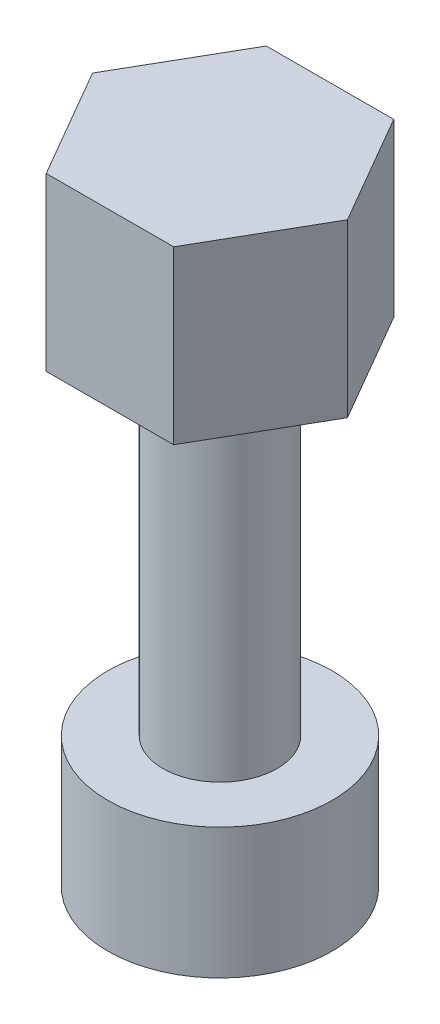
SolidWorks part; units mm, degrees
ref_plane "Front Plane" through (0, 0, 0) normal (0, 0, 1) x (1, 0, 0)
ref_plane "Top Plane" through (0, 0, 0) normal (0, 1, 0) x (1, 0, 0)
ref_plane "Right Plane" through (0, 0, 0) normal (1, 0, 0) x (0, 0, -1)
sketch "Sketch1" plane through (0, 0, 0) normal (0, 1, 0) x (1, 0, 0)
  circle A0 centre (0, 0) radius 2.75
  dimension "D1" = 5.5
extrude "Boss-Extrude1" add sketch "Sketch1" along normal blind 3.2
sketch "Sketch2" plane through (0, 3.2, 0) normal (0, 1, 0) x (1, 0, 0)
  circle A0 centre (0, 0) radius 1.4
  dimension "D1" = 2.8
extrude "Boss-Extrude2" add sketch "Sketch2" along normal blind 8.3
sketch "Sketch3" plane through (0, 11.5, 0) normal (0, 1, 0) x (1, 0, 0)
  line L1 (1.5546, 2.7024) -> (-1.563, 2.6976)
  line L2 (-1.563, 2.6976) -> (-3.1177, -0.0048)
  line L3 (-3.1177, -0.0048) -> (-1.5546, -2.7024)
  line L4 (-1.5546, -2.7024) -> (1.563, -2.6976)
  line L5 (1.563, -2.6976) -> (3.1177, 0.0048)
  line L6 (3.1177, 0.0048) -> (1.5546, 2.7024)
  circle A0 centre (0, 0) radius 2.7 construction
  dimension "D1" = 5.4
extrude "Boss-Extrude3" add sketch "Sketch3" along normal blind 4.2
